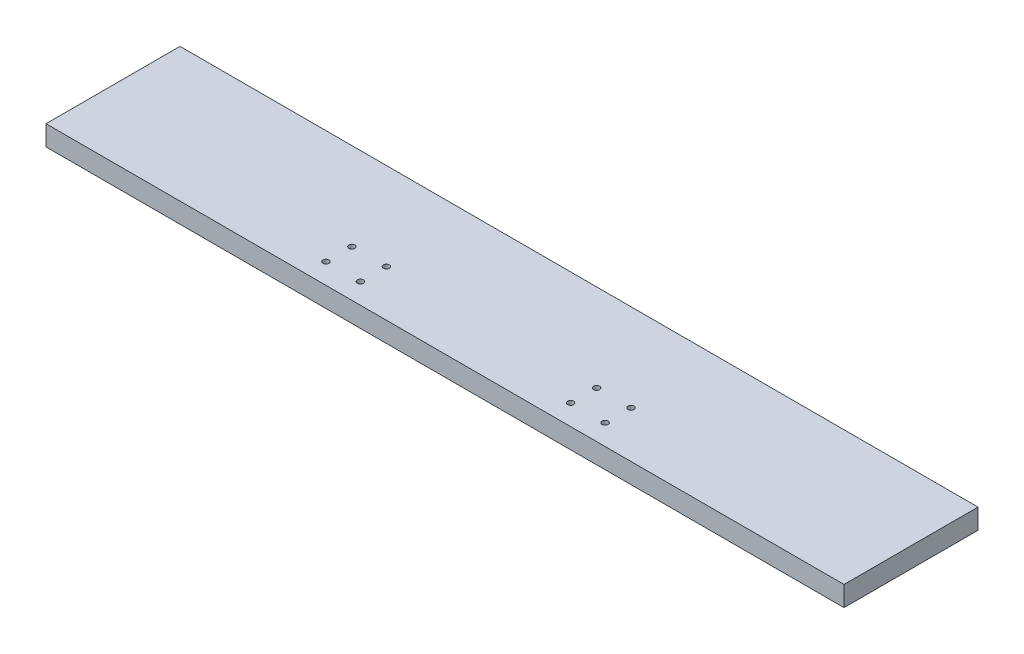
SolidWorks part; units mm, degrees
ref_plane "Front Plane" through (0, 0, 0) normal (0, 0, 1) x (1, 0, 0)
ref_plane "Top Plane" through (0, 0, 0) normal (0, 1, 0) x (1, 0, 0)
ref_plane "Right Plane" through (0, 0, 0) normal (1, 0, 0) x (0, 0, -1)
sketch "Sketch2" plane through (0, 0, 0) normal (0, 1, 0) x (1, 0, 0)
  line L1 (0, 0) -> (756.412, 0)
  line L2 (0, 0) -> (0, 127)
  line L3 (0, 127) -> (756.412, 127)
  line L4 (756.412, 0) -> (756.412, 127)
  dimension "D1" = 127
  dimension "D2" = 756.412
extrude "Boss-Extrude1" add sketch "Sketch2" along normal blind 19.05
sketch "Sketch3" plane through (0, 19.05, 0) normal (0, 1, 0) x (1, 0, 0)
  circle A0 centre (245.9291, 19.4627) radius 2.8512
  circle A1 centre (278.5808, 19.4627) radius 2.8511
  circle A2 centre (278.5808, 44.0372) radius 2.8511
  circle A3 centre (245.9291, 44.0372) radius 2.8512
  circle A4 centre (477.8311, 19.4628) radius 2.8511
  circle A5 centre (510.4828, 19.4628) radius 2.8511
  circle A6 centre (510.4828, 44.0373) radius 2.8511
  circle A7 centre (477.8311, 44.0373) radius 2.8511
extrude "Cut-Extrude1" cut sketch "Sketch3" against normal up to next
